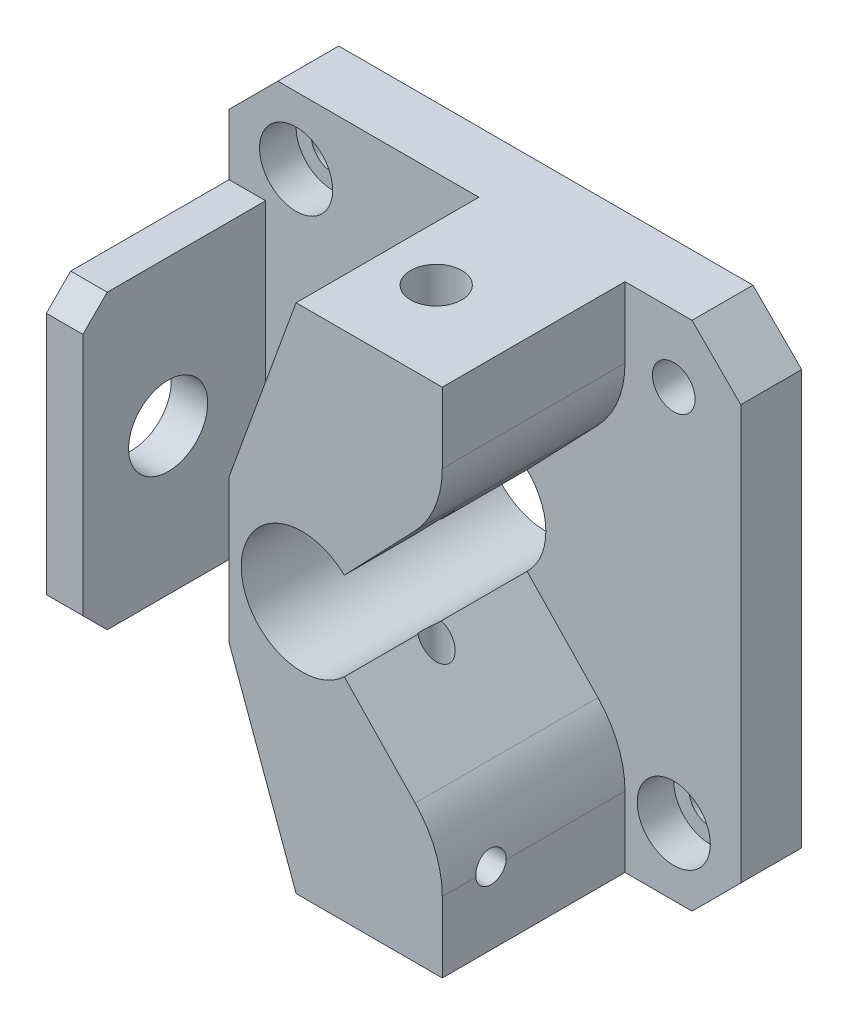
SolidWorks part; units mm, degrees
material "6063-T1"
ref_plane "Piano frontale" through (0, 0, 0) normal (0, 0, 1) x (1, 0, 0)
ref_plane "Piano superiore" through (0, 0, 0) normal (0, 1, 0) x (1, 0, 0)
ref_plane "Piano destro" through (0, 0, 0) normal (1, 0, 0) x (0, 0, -1)
ref_plane "Motor plane" through (0, 0, -20) normal (0, 0, 1) x (1, 0, 0)
sketch "Schizzo1" plane through (0, 0, -20) normal (0, 0, 1) x (1, 0, 0)
  line L1 (15.5, -15.5) -> (-15.5, -15.5) construction
  line L2 (15.5, -15.5) -> (15.5, 15.5) construction
  line L3 (15.5, 15.5) -> (-15.5, 15.5) construction
  line L4 (-15.5, -15.5) -> (-15.5, 15.5) construction
  line L5 (15.5, -15.5) -> (-15.5, 15.5) construction
  line L6 (15.5, 15.5) -> (-15.5, -15.5) construction
  line L7 (21, -21) -> (-21, -21)
  line L8 (21, -21) -> (21, 21)
  line L9 (21, 21) -> (-21, 21)
  line L10 (-21, -21) -> (-21, 21)
  line L11 (21, -21) -> (-21, 21) construction
  line L12 (21, 21) -> (-21, -21) construction
  circle A0 centre (-15.5, 15.5) radius 1.75
  circle A1 centre (15.5, 15.5) radius 1.75
  circle A2 centre (-15.5, -15.5) radius 1.75
  circle A3 centre (15.5, -15.5) radius 1.75
  dimension "D3" = 3.5
  dimension "D1" = 31
  dimension "D2" = 31
  dimension "D5" = 42
  dimension "D6" = 42
extrude "Estrusione-Estrusione1" add sketch "Schizzo1" along normal blind 5
sketch "Schizzo3" plane through (0, 0, -15) normal (0, 0, 1) x (1, 0, 0)
  line L0 (-21, -21) -> (21, -21) construction
  line L1 (11.5, -21) -> (-6, -21)
  line L2 (11.5, -21) -> (11.5, 21)
  line L3 (11.5, 21) -> (-6, 21)
  line L4 (-6, -21) -> (-6, 21)
  line L5 (21, 21) -> (-21, 21) construction
  line L6 (-21, 21) -> (-21, -21) construction
  line L7 (21, -21) -> (21, 21) construction
  dimension "D1" = 15
  dimension "D2" = 9.5
extrude "Estrusione-Estrusione4" add sketch "Schizzo3" along normal blind 15
sketch "Schizzo4" plane through (0, 0, 0) normal (0, 0, 1) x (1, 0, 0)
  circle A0 centre (0, 0) radius 5
  dimension "D1" = 10
extrude "Taglio-Estrusione1" cut sketch "Schizzo4" against normal through all
ref_plane "Piano3" through (4, 0, 0) normal (1, 0, 0) x (0, 0, -1)
sketch "Schizzo6" plane through (0, -21, 0) normal (0, -1, 0) x (1, 0, 0)
  line L0 (11.5, -7) -> (-6, -7) construction
  line L2 (-6, 0) -> (-6, -15) construction
  line L3 (4, -11) -> (4, 11) construction
  line L4 (4, -2.5823) -> (4, -27.3722) construction
  line L9 (23.1, -20) -> (-23.1, -20) construction
  circle A0 centre (4, -7) radius 1.1
  point P10 (4, -7)
  dimension "D1" = 2.2
  dimension "D2" = 13
extrude "Taglio-Estrusione3" cut sketch "Schizzo6" against normal through all
sketch "Schizzo7" plane through (0, 0, 0) normal (0, 0, 1) x (1, 0, 0)
  line L0 (11.5, 0) -> (-6, 0) construction
  line L1 (11.5, -21) -> (11.5, 21) construction
  line L2 (-6, 21) -> (-6, -21) construction
  line L3 (11.5, 12) -> (0, 0)
  line L4 (11.5, 12) -> (11.5, -12)
  line L5 (11.5, -12) -> (0, 0)
  dimension "D1" = 12
extrude "Taglio-Estrusione4" cut sketch "Schizzo7" against normal blind 15
fillet "Raccordo2" radius 8 1 edges at (11.5, 12, -7.5)
fillet "Raccordo3" radius 8 1 edges at (11.5, -12, -7.5)
chamfer "Smusso1" distance 4 angle 45 4 edges at (21, -21, -17.5) (-21, -21, -17.5) (-21, 21, -17.5) (21, 21, -17.5)
sketch "Schizzo22" plane through (11.5, 0, 0) normal (1, 0, 0) x (0, 0, -1)
  line L0 (15, -17) -> (15, 17) construction
  point P0 (4, -15.1119)
  dimension "D1" = 11
hole_wizard "Foro filettato M3-2" positions "Schizzo24" profile "Schizzo23" tap size "M3" standard "ISO"
sketch "Schizzo24" plane through (11.5, 0, 0) normal (1, 0, 0) x (0, 0, -1)
  point P0 (4, -15.1119)
sketch "Schizzo23" plane through (11.5, -15.1119, -4) normal (0, 1, 0) x (0, 0, -1)
  line L0 (0, 0) -> (0, 12.7511)
  line L1 (0, 12.7511) -> (1.25, 12)
  line L2 (1.25, 12) -> (1.25, 0)
  line L5 (1.25, 0) -> (0, 0)
  line L10 (0, 12.7511) -> (-1.25, 12) construction
  line L11 (0, -6.35) -> (0, 107.95) construction
  dimension "Tap Drill Dia." = 2.5
  dimension "Tap Drill Depth" = 12
  dimension "Drill Angle" = 118
cosmetic thread "Filettatura del foro2" parameters "D1"=6, "D2"=3
sketch "Schizzo28" plane through (0, 0, -15) normal (0, 0, 1) x (1, 0, 0)
  line L1 (-21, 0) -> (21, 0) construction
  line L2 (-21, 17) -> (-21, -17) construction
  line L3 (21, -17) -> (21, 17) construction
  line L4 (-21, -12) -> (-21, 12)
  line L6 (-21, 12) -> (-18, 12)
  line L7 (-18, 12) -> (-18, -12)
  line L8 (-21, -12) -> (-18, -12)
  point P13 (-18, 0)
  dimension "D1" = 3
  dimension "D2" = 12
extrude "Estrusione-Estrusione5" add sketch "Schizzo28" along normal blind 15
sketch "Schizzo29" plane through (0, 0, -15) normal (0, 0, 1) x (1, 0, 0)
  circle A0 centre (-15.5, 15.5) radius 3
  circle A1 centre (-15.5, -15.5) radius 3
  circle A2 centre (15.5, -15.5) radius 3
  dimension "D1" = 6
extrude "Taglio-Estrusione6" cut sketch "Schizzo29" against normal blind 3
chamfer "Smusso3" distance 5.5 angle 70 2 edges first distance on face at (5.1, -21, -7) first distance on face at (5.1, 21, -7)
sketch "Schizzo30" plane through (-21, 0, 0) normal (-1, 0, 0) x (0, 0, 1)
  line L0 (0, 0) -> (-20, 0) construction
  line L1 (0, 12) -> (0, -12) construction
  line L2 (-20, -23.1) -> (-20, 23.1) construction
  circle A0 centre (-7, 0) radius 3.25
  dimension "D1" = 6.5
  dimension "D2" = 7
extrude "Taglio-Estrusione7" cut sketch "Schizzo30" against normal blind 3
chamfer "Smusso4" distance 2 angle 45 2 edges at (-19.5, -12, 0) (-19.5, 12, 0)
hole_wizard "Foro filettato M5-1" positions "Schizzo3D1" profile "Schizzo31" tap size "M5" standard "ISO"
sketch3d "Schizzo3D1"
  line L0 (4, 21, -7) -> (4, 3.6099, -7) construction
  point P0 (4, 21, -7)
sketch "Schizzo31" plane through (4, 21, -7) normal (1, 0, 0) x (0, 0, 1)
  line L0 (0, 0) -> (0, 6.2618)
  line L1 (0, 6.2618) -> (2.1, 5)
  line L2 (2.1, 5) -> (2.1, 0)
  line L5 (2.1, 0) -> (0, 0)
  line L10 (0, 6.2618) -> (-2.1, 5) construction
  line L11 (0, -6.35) -> (0, 107.95) construction
  dimension "Tap Drill Dia." = 4.2
  dimension "Tap Drill Depth" = 5
  dimension "Drill Angle" = 118
cosmetic thread "Filettatura del foro3" parameters "D1"=5, "D2"=5
